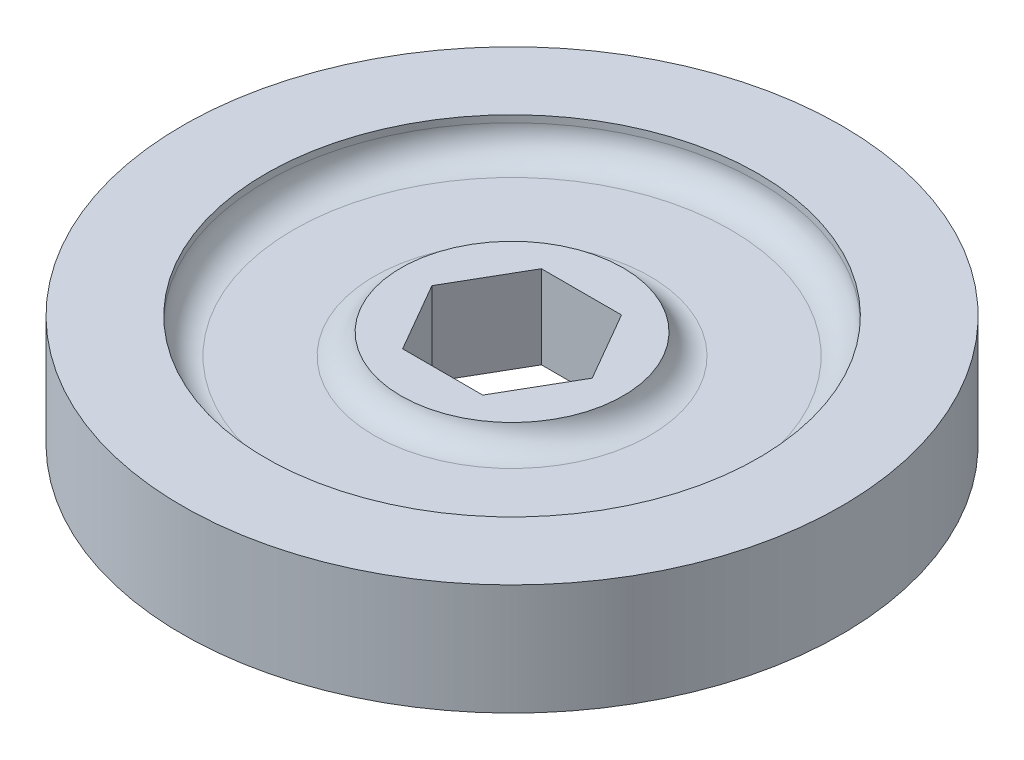
SolidWorks part; units mm, degrees
material "Rubber"
ref_plane "Front Plane" through (0, 0, 0) normal (0, 0, 1) x (1, 0, 0)
ref_plane "Top Plane" through (0, 0, 0) normal (0, 1, 0) x (1, 0, 0)
ref_plane "Right Plane" through (0, 0, 0) normal (1, 0, 0) x (0, 0, -1)
sketch "Sketch1" plane through (0, 0, 0) normal (0, 0, 1) x (1, 0, 0)
  line L0 (0, 0) -> (0, 9.2164) construction
  line L1 (10.16, -1.905) -> (10.16, -3.81)
  line L2 (0, 3.81) -> (10.16, 3.81)
  line L3 (0, 3.81) -> (0, -3.81)
  line L4 (0, -3.81) -> (10.16, -3.81)
  line L5 (10.16, 3.81) -> (10.16, 1.905)
  line L6 (10.16, 1.905) -> (22.5425, 1.905)
  line L7 (22.5425, -1.905) -> (22.5425, -5.08)
  line L8 (10.16, -1.905) -> (22.5425, -1.905)
  line L10 (22.5425, 5.08) -> (30.1625, 5.08)
  line L11 (22.5425, 5.08) -> (22.5425, 1.905)
  line L12 (22.5425, -5.08) -> (30.1625, -5.08)
  line L13 (30.1625, 5.08) -> (30.1625, -5.08)
  point P15 (22.5425, 6.1614)
  point P16 (0, 0)
  dimension "D1" = 7.62
  dimension "D2" = 10.16
  dimension "D3" = 3.81
  dimension "D4" = 22.5425
  dimension "D5" = 30.1625
  dimension "D6" = 10.16
revolve "Revolve1" add sketch "Sketch1" angle 360 about L0
fillet "Fillet1" radius 2.54 2 edges at (0, 1.905, -22.5425) (0, 1.905, -10.16)
fillet "Fillet2" radius 2.54 2 edges at (0, -1.905, -10.16) (0, -1.905, -22.5425)
sketch "Sketch2" plane through (0, -3.81, 0) normal (0, -1, 0) x (1, 0, 0)
  line L1 (3.6662, 6.35) -> (-3.6662, 6.35)
  line L2 (-3.6662, 6.35) -> (-7.3323, 0)
  line L3 (-7.3323, 0) -> (-3.6662, -6.35)
  line L4 (-3.6662, -6.35) -> (3.6662, -6.35)
  line L5 (3.6662, -6.35) -> (7.3323, 0)
  line L6 (7.3323, 0) -> (3.6662, 6.35)
  circle A0 centre (0, 0) radius 6.35 construction
  dimension "D1" = 12.7
extrude "Cut-Extrude1" cut sketch "Sketch2" against normal through all
